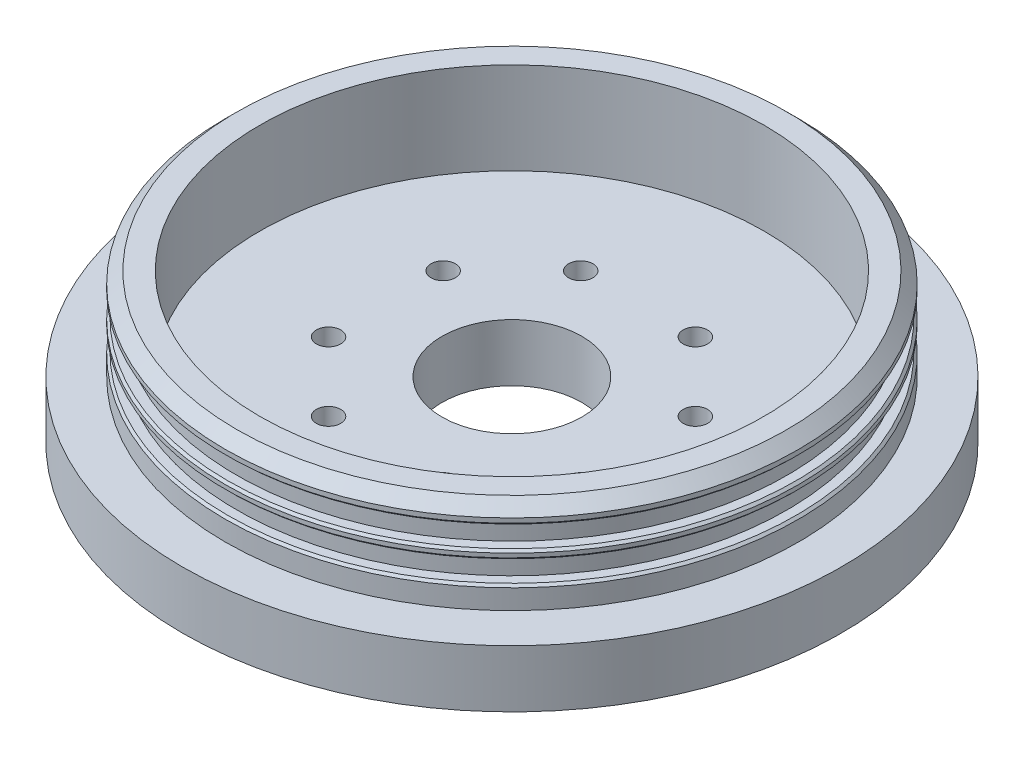
SolidWorks part; units mm, degrees
material "6061 Alloy"
ref_plane "Front Plane" through (0, 0, 0) normal (0, 0, 1) x (1, 0, 0)
ref_plane "Top Plane" through (0, 0, 0) normal (0, 1, 0) x (1, 0, 0)
ref_plane "Right Plane" through (0, 0, 0) normal (1, 0, 0) x (0, 0, -1)
sketch "Sketch1" plane through (0, 0, 0) normal (0, 1, 0) x (1, 0, 0)
  circle A0 centre (0, 0) radius 36.5125
extrude "Extrude1" add sketch "Sketch1" along normal blind 3.175 and the other way blind 3.175
sketch "Sketch2" plane through (0, 3.175, 0) normal (0, 1, 0) x (-1, 0, 0)
  circle A0 centre (0, 0) radius 31.75
extrude "Extrude2" add sketch "Sketch2" along normal blind 10.16
sketch "Sketch4" plane through (0, 0, 0) normal (1, 0, 0) x (0, 0, -1)
  line L0 (-31.75, 13.335) -> (-31.75, 3.175) construction
  line L1 (-31.75, 11.3034) -> (-30.48, 11.3034)
  line L2 (-31.75, 11.3034) -> (-31.75, 8.9412)
  line L3 (-31.75, 8.9412) -> (-30.48, 8.9412)
  line L4 (-30.48, 11.3034) -> (-30.48, 8.9412)
  line L5 (0, -3.175) -> (0, 13.8799) construction
  line L6 (-31.75, 7.9811) -> (-30.48, 7.9811)
  line L7 (-31.75, 7.9811) -> (-31.75, 5.6189)
  line L8 (-31.75, 5.6189) -> (-30.48, 5.6189)
  line L9 (-30.48, 7.9811) -> (-30.48, 5.6189)
  line L10 (-36.5125, -3.175) -> (36.5125, -3.175) construction
  dimension "D1" = 2.3622
  dimension "D2" = 2.3622
  dimension "D3" = 30.48
revolve "Cut-Revolve7" cut sketch "Sketch4" angle 360 about L5
sketch "Sketch5" plane through (0, 13.335, 0) normal (0, 1, 0) x (-1, 0, 0)
  circle A0 centre (0, 0) radius 27.94
extrude "Cut-Extrude1" cut sketch "Sketch5" against normal blind 10.16
chamfer "Chamfer1" distance 1.27 angle 45 1 edges at (0, 13.335, 31.75)
sketch "Sketch8" plane through (0, 0, 0) normal (0, 1, 0) x (1, 0, 0)
  line L0 (0, 0) -> (0, 36.5125) construction
  circle A0 centre (0, 0) radius 36.5125 construction
hole_wizard "M14 Clearance Hole1" positions "3DSketch1" profile "Sketch9" hole size "M14" standard "Ansi Metric"
sketch3d "3DSketch1"
  point P0 (0, 0, 0)
  point P4 (0, -3.175, 0)
sketch "Sketch9" plane through (0, -3.175, 0) normal (1, 0, 0) x (0, 0, -1)
  line L0 (0, 0) -> (0, 334.8567)
  line L1 (0, 334.8567) -> (7.75, 330.2)
  line L2 (7.75, 330.2) -> (7.75, 0)
  line L5 (7.75, 0) -> (0, 0)
  line L10 (0, 334.8567) -> (-7.75, 330.2) construction
  line L11 (0, -6.35) -> (0, 107.95) construction
  dimension "Hole Dia." = 15.5
  dimension "Hole Depth" = 330.2
  dimension "Drill Angle" = 118
chamfer "Chamfer2" distance 0.254 angle 45 4 edges at (0, 11.3034, -31.75) (0, 5.6189, -31.75) (0, 7.9811, -31.75) (0, 8.9412, -31.75)
hole_wizard "Tap Drill for #6 Tap1" positions "3DSketch2" profile "Sketch11" hole size "#6-32" standard "Ansi Inch"
sketch3d "3DSketch2"
  line L10 (-13.97, 3.175, -6.35) -> (13.97, 3.175, -6.35) construction
  line L11 (13.97, 3.175, -6.35) -> (13.97, 3.175, 6.35) construction
  line L12 (13.97, 3.175, 6.35) -> (-13.97, 3.175, 6.35) construction
  line L13 (-13.97, 3.175, 6.35) -> (-13.97, 3.175, -6.35) construction
  line L15 (-6.35, 3.175, 13.97) -> (-6.35, 3.175, -13.97) construction
  line L16 (-6.35, 3.175, -13.97) -> (6.35, 3.175, -13.97) construction
  line L17 (6.35, 3.175, -13.97) -> (6.35, 3.175, 13.97) construction
  line L18 (6.35, 3.175, 13.97) -> (-6.35, 3.175, 13.97) construction
  line L24 (0, 3.175, -13.97) -> (0, 3.175, 13.97) construction
  line L26 (13.97, 3.175, 0) -> (-13.97, 3.175, 0) construction
  point P0 (-6.35, 3.175, 13.97)
  point P2 (6.35, 3.175, 13.97)
  point P27 (13.97, 3.175, 6.35)
  point P29 (13.97, 3.175, -6.35)
  point P31 (6.35, 3.175, -13.97)
  point P33 (-6.35, 3.175, -13.97)
  point P35 (-13.97, 3.175, -6.35)
  point P37 (-13.97, 3.175, 6.35)
  point P56 (0, 0, 0)
  point P65 (0, 3.175, 0)
  dimension "D1" = 27.94
  dimension "D2" = 12.7
  dimension "D3" = 27.94
  dimension "D4" = 13.97
  dimension "D5" = 13.97
  dimension "D7" = 12.7
sketch "Sketch11" plane through (-6.35, 3.175, 13.97) normal (1, 0, 0) x (0, 0, 1)
  line L0 (0, 0) -> (0, 4.1147)
  line L1 (0, 4.1147) -> (1.3525, 3.302)
  line L2 (1.3525, 3.302) -> (1.3525, 0)
  line L5 (1.3525, 0) -> (0, 0)
  line L10 (0, 4.1147) -> (-1.3526, 3.302) construction
  line L11 (0, -6.35) -> (0, 107.95) construction
  dimension "Hole Dia." = 2.7051
  dimension "Hole Depth" = 3.302
  dimension "Drill Angle" = 118
